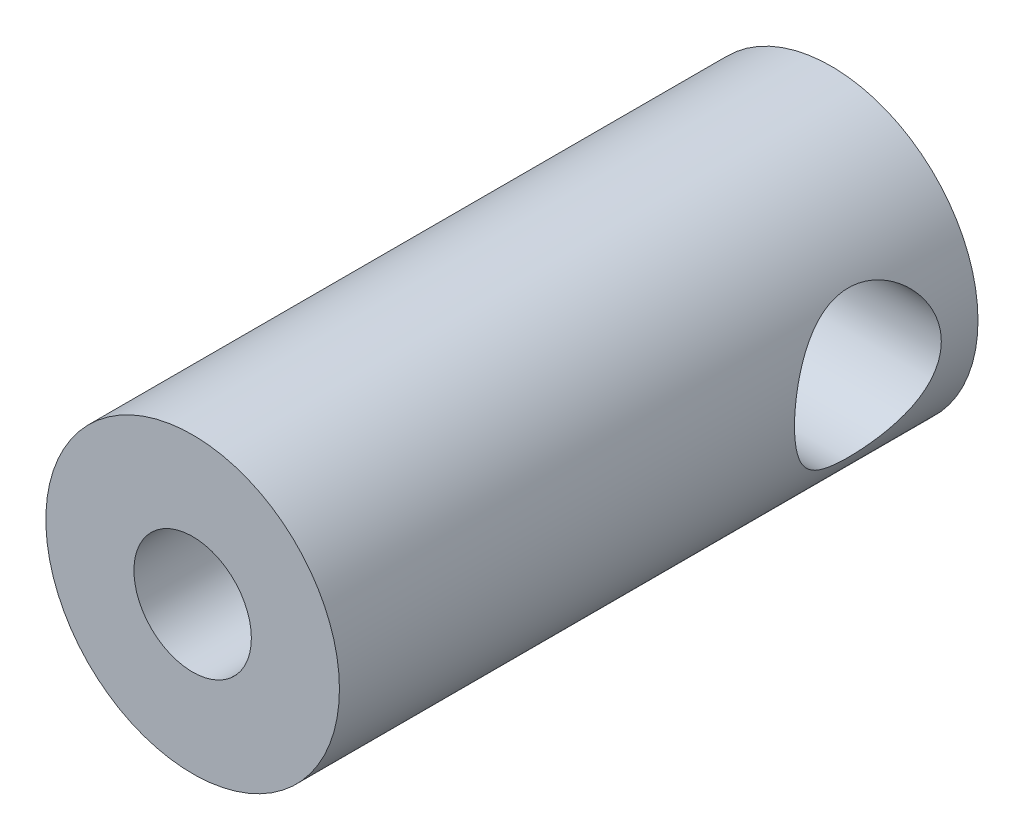
SolidWorks part; units mm, degrees
note: The reader was unsure of these and kept them because the rebuilt part matched: shared geometry of "Sketch2<2>".
ref_plane "Front Plane" through (0, 0, 0) normal (0, 0, 1) x (1, 0, 0)
ref_plane "Top Plane" through (0, 0, 0) normal (0, 1, 0) x (1, 0, 0)
ref_plane "Right Plane" through (0, 0, 0) normal (1, 0, 0) x (0, 0, -1)
sketch "Sketch1" plane through (0, 0, 0) normal (0, 0, 1) x (1, 0, 0)
  circle A0 centre (0, 0) radius 6.35
  dimension "D1" = 12.7
extrude "Boss-Extrude1" add sketch "Sketch1" along normal blind 27.6225
sketch "Sketch2" plane through (0, 0, 27.6225) normal (0, 0, 1) x (1, 0, 0)
  circle A0 centre (0, 0) radius 2.54
  dimension "D1" = 5.08
extrude "Cut-Extrude1" [suppressed] cut sketch "Sketch2" against normal blind 12.7
sketch "Sketch3" plane through (0, 0, 0) normal (1, 0, 0) x (0, 0, -1)
  line L0 (-27.6225, 6.35) -> (-27.6225, -6.35) construction
  circle A0 centre (-4.7625, 0) radius 3.175
  dimension "D2" = 6.35
  dimension "D1" = 22.86
extrude "Cut-Extrude2" cut sketch "Sketch3" against normal through all and the other way through all
hole_wizard "#6-32 Tapped Hole1" [suppressed] positions "Sketch5" profile "Sketch6" tap size "#6-32" standard "ANSI Inch"
sketch "Sketch5" plane through (0, 0, 27.6225) normal (0, 0, 1) x (1, 0, 0)
  point P0 (0, 0)
sketch "Sketch6" plane through (0, 0, 27.6225) normal (1, 0, 0) x (0, -1, 0)
  line L0 (0, 0) -> (0, 13.5127)
  line L1 (0, 13.5127) -> (1.3525, 12.7)
  line L2 (1.3525, 12.7) -> (1.3525, 0)
  line L5 (1.3525, 0) -> (0, 0)
  line L10 (0, 13.5127) -> (-1.3526, 12.7) construction
  line L11 (0, -6.35) -> (0, 107.95) construction
  dimension "Tap Drill Dia." = 2.7051
  dimension "Tap Drill Depth" = 12.7
  dimension "Drill Angle" = 118
cosmetic thread "Hole Thread1" [suppressed] parameters "D1"=1.0644, "D2"=3.5052
extrude "Cut-Extrude3" cut sketch "Sketch2<2>" against normal blind 12.7
sketch "Sketch2<2>" plane through (0, 0, 27.6225) normal (0, 0, 1) x (1, 0, 0) same geometry as "Sketch2"
